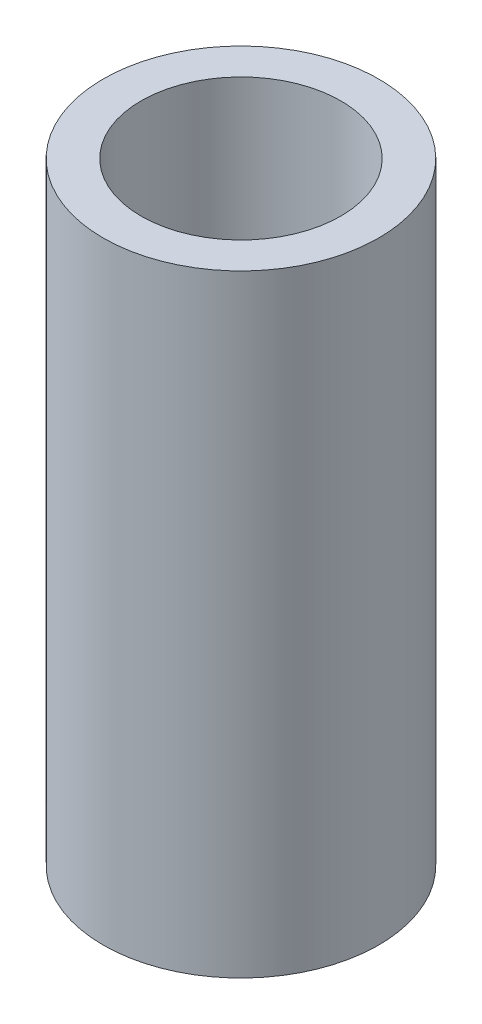
SolidWorks part; units mm, degrees
ref_plane "Front Plane" through (0, 0, 0) normal (0, 0, 1) x (1, 0, 0)
ref_plane "Top Plane" through (0, 0, 0) normal (0, 1, 0) x (1, 0, 0)
ref_plane "Right Plane" through (0, 0, 0) normal (1, 0, 0) x (0, 0, -1)
sketch "Sketch1" plane through (0, 0, 0) normal (0, 1, 0) x (1, 0, 0)
  circle A0 centre (0, 0) radius 2
  circle A1 centre (0, 0) radius 1.45
  dimension "D1" = 4
  dimension "D2" = 2.9
extrude "Boss-Extrude1" add sketch "Sketch1" along normal blind 8.89
